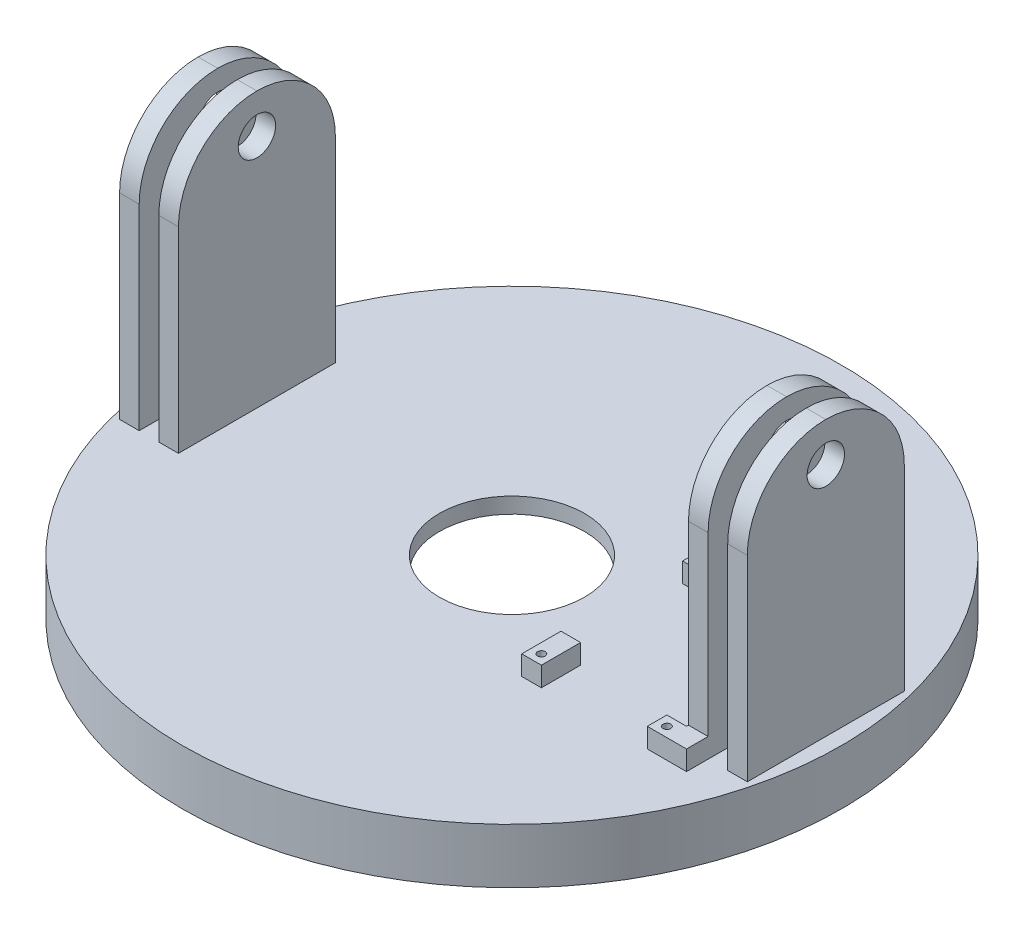
SolidWorks part; units mm, degrees
ref_plane "Alzado" through (0, 0, 0) normal (0, 0, 1) x (1, 0, 0)
ref_plane "Planta" through (0, 0, 0) normal (0, 1, 0) x (1, 0, 0)
ref_plane "Vista lateral" through (0, 0, 0) normal (1, 0, 0) x (0, 0, -1)
sketch "Croquis1" plane through (0, 0, 0) normal (0, 1, 0) x (1, 0, 0)
  circle A0 centre (0, 0) radius 84
  circle A1 centre (0, 0) radius 82
  dimension "D1" = 168
  dimension "D2" = 164
extrude "Saliente-Extruir1" add sketch "Croquis1" along normal blind 10
sketch "Croquis2" plane through (0, 10, 0) normal (0, 1, 0) x (1, 0, 0)
  circle A0 centre (0, 0) radius 84
  dimension "D1" = 168
extrude "Saliente-Extruir2" add sketch "Croquis2" along normal blind 4
sketch "Croquis3" plane through (0, 10, 0) normal (0, -1, 0) x (1, 0, 0)
  circle A0 centre (-20, 40) radius 1.5
  dimension "D1" = 3
  dimension "D6" = 40
  dimension "D7" = 20
extrude "Saliente-Extruir3" add sketch "Croquis3" along normal blind 10
ref_axis "Eje1" through (0, -0.7, 0) along (0, 1, 0)
pattern_circular "MatrizC1" count 4 every 90 about axis through (0, -0.7, 0) along (0, 1, 0) of "Saliente-Extruir3"
sketch "Croquis15" plane through (0, 0, 0) normal (0, -1, 0) x (1, 0, 0)
  circle A0 centre (0, 0) radius 82
  circle A1 centre (0, 0) radius 83
  dimension "D1" = 164
  dimension "D2" = 166
extrude "Cortar-Extruir1" cut sketch "Croquis15" against normal blind 5
sketch "Croquis16" plane through (0, 10, 0) normal (0, -1, 0) x (1, 0, 0)
  circle A0 centre (0, 0) radius 18.5
  dimension "D1" = 37
extrude "Cortar-Extruir2" cut sketch "Croquis16" against normal blind 13 contours A0
sketch "Croquis18" plane through (0, 14, 0) normal (0, 1, 0) x (1, 0, 0)
  line L0 (0, 0) -> (-84, 0) construction
  line L1 (0, 0) -> (0, 84) construction
  line L3 (-80, -20) -> (-65, -20)
  line L4 (-80, -20) -> (-80, 20)
  line L5 (-80, 20) -> (-65, 20)
  line L6 (-65, -20) -> (-65, 20)
  line L7 (-80, -20) -> (-65, 20) construction
  line L8 (-80, 20) -> (-65, -20) construction
  circle A0 centre (0, 0) radius 84 construction
  point P6 (-72.5, 0)
  dimension "D1" = 15
  dimension "D2" = 40
  dimension "D3" = 65
extrude "Saliente-Extruir4" add sketch "Croquis18" along normal blind 70
sketch "Croquis19" plane through (0, 84, 0) normal (0, 1, 0) x (1, 0, 0)
  line L0 (-65, 20) -> (-80, 20) construction
  line L1 (-75, 20) -> (-70, 20)
  line L2 (-75, 20) -> (-75, -20)
  line L3 (-75, -20) -> (-70, -20)
  line L4 (-70, 20) -> (-70, -20)
  line L5 (-80, -20) -> (-65, -20) construction
  line L6 (-80, 20) -> (-80, -20) construction
  dimension "D2" = 5
  dimension "D3" = 5
extrude "Cortar-Extruir3" cut sketch "Croquis19" against normal blind 70
sketch "Croquis20" plane through (-80, 0, 0) normal (-1, 0, 0) x (0, 0, 1)
  line L0 (-20, 84) -> (20, 84) construction
  line L1 (-20, 84) -> (-20, 14) construction
  circle A0 centre (0, 74) radius 4.7625
  dimension "D3" = 9.525
  dimension "D1" = 10
  dimension "D2" = 20
extrude "Cortar-Extruir4" cut sketch "Croquis20" against normal blind 40
fillet "Redondeo2" radius 20 4 edges at (-77.5, 84, 20) (-67.5, 84, 20) (-67.5, 84, -20) (-77.5, 84, -20)
mirror "Simetría1" about plane through (0, 0, 0) normal (1, 0, 0) of "Saliente-Extruir4", "Redondeo2", "Cortar-Extruir4", "Cortar-Extruir3"
sketch "Croquis21" plane through (65, 0, 0) normal (-1, 0, 0) x (0, 0, 1)
  line L0 (-20, 64) -> (-20, 14) construction
  line L2 (20, 14) -> (-20, 14) construction
  circle A0 centre (0, 34.5) radius 5
  dimension "D2" = 20.5
  dimension "D3" = 10
  dimension "D1" = 20
extrude "Cortar-Extruir5" cut sketch "Croquis21" against normal blind 10
sketch "Croquis22" plane through (0, 14, 0) normal (0, 1, 0) x (1, 0, 0)
  line L0 (0, 0) -> (-84, 0) construction
  line L1 (0, 0) -> (0, 84) construction
  line L2 (65, -20) -> (65, 20) construction
  line L7 (28, -15.5) -> (33, -15.5)
  line L9 (70, -25.5) -> (70, -20)
  line L11 (28, -25.5) -> (28, -15.5)
  line L12 (65, -20) -> (65, -20.5)
  line L14 (33, -15.5) -> (33, -25.5)
  line L16 (33, 25.5) -> (28, 25.5)
  line L20 (28, 15.5) -> (28, 25.5)
  line L21 (33, -25.5) -> (28, -25.5)
  line L22 (33, 25.5) -> (33, 15.5)
  line L23 (28, 15.5) -> (33, 15.5)
  line L25 (70, 20) -> (70, 25.5)
  line L27 (70, -20) -> (65, -20)
  line L28 (60, -20.5) -> (60, -25.5)
  line L29 (70, -25.5) -> (60, -25.5)
  line L30 (70, 20) -> (65, 20)
  line L31 (60, 20.5) -> (60, 25.5)
  line L32 (60, 25.5) -> (70, 25.5)
  line L34 (65, 20) -> (65, 20.5)
  line L35 (65, 20.5) -> (60, 20.5)
  line L36 (65, -20.5) -> (60, -20.5)
  circle A0 centre (0, 0) radius 84 construction
  point P5 (30.5, -25.5)
  dimension "D2" = 42
  dimension "D3" = 42
  dimension "D4" = 10
  dimension "D5" = 51
  dimension "D6" = 5.5
  dimension "D7" = 5.5
  dimension "D8" = 32
  dimension "D9" = 10
  dimension "D10" = 5
  dimension "D11" = 5
  dimension "D12" = 5
  dimension "D13" = 5
  dimension "D14" = 0.5
  dimension "D15" = 5
  dimension "D16" = 0.5
  dimension "D17" = 5
  dimension "D18" = 41
  dimension "D19" = 31
extrude "Saliente-Extruir6" add sketch "Croquis22" along normal blind 5
sketch "Croquis24" plane through (0, 14, 0) normal (0, 1, 0) x (1, 0, 0)
  line L0 (33, -25.5) -> (33, -15.5) construction
  line L2 (33, 25.5) -> (28, 25.5) construction
  line L3 (28, 25.5) -> (28, 15.5) construction
  line L4 (70, 25.5) -> (60, 25.5) construction
  line L5 (60, 25.5) -> (60, 20.5) construction
  line L6 (65, -20.5) -> (60, -20.5) construction
  line L7 (60, -20.5) -> (60, -25.5) construction
  line L9 (28, -25.5) -> (33, -25.5) construction
  circle A0 centre (30.5, 23) radius 0.9769
  circle A1 centre (62.5, 23) radius 0.9769
  circle A2 centre (30.5, -23) radius 0.9769
  circle A3 centre (62.5, -23) radius 0.9769
  dimension "D1" = 1.9538
  dimension "D2" = 1.9538
  dimension "D3" = 1.9538
  dimension "D4" = 1.9538
  dimension "D5" = 2.5
  dimension "D6" = 2.5
  dimension "D7" = 2.5
  dimension "D8" = 2.5
  dimension "D9" = 2.5
  dimension "D10" = 2.5
  dimension "D11" = 2.5
  dimension "D12" = 2.5
extrude "Cortar-Extruir6" cut sketch "Croquis24" along normal blind 6
